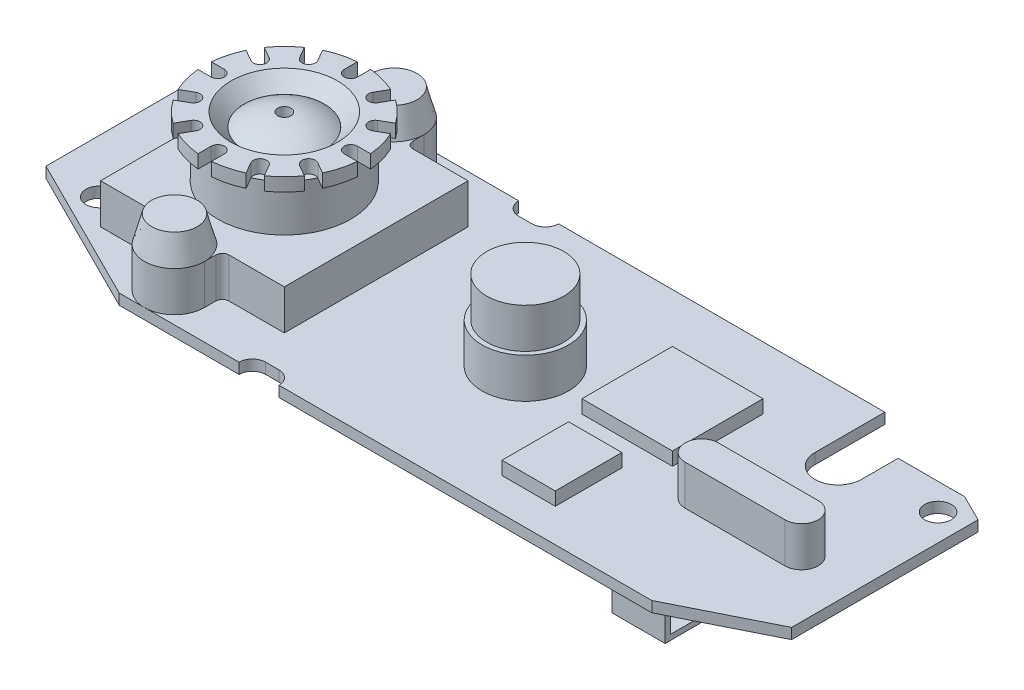
SolidWorks part; units mm, degrees
ref_plane "前基準面" through (0, 0, 0) normal (0, 0, 1) x (1, 0, 0)
ref_plane "上基準面" through (0, 0, 0) normal (0, 1, 0) x (1, 0, 0)
ref_plane "右基準面" through (0, 0, 0) normal (1, 0, 0) x (0, 0, -1)
sketch "草圖1" plane through (0, 0, 0) normal (0, 1, 0) x (1, 0, 0)
  line L0 (0, 0) -> (40355.7531, 0) construction
  line L1 (-20, -10.5) -> (20, -10.5)
  line L2 (20, -10.5) -> (31, -5)
  line L3 (31, -5) -> (31, 5)
  line L4 (31, 5) -> (20, 10.5)
  line L5 (20, 10.5) -> (-20, 10.5)
  line L6 (-20, 10.5) -> (-31, 5)
  line L7 (-31, 5) -> (-31, -5)
  line L8 (-31, -5) -> (-20, -10.5)
  dimension "D1" = 40
  dimension "D2" = 11
  dimension "D3" = 11
  dimension "D4" = 21
  dimension "D5" = 10
  dimension "D6" = 31
  dimension "D7" = 10
extrude "填料-伸長1" add sketch "草圖1" along normal mid plane 0.8
sketch "草圖3" plane through (0, 0.4, 0) normal (0, 1, 0) x (1, 0, 0)
  circle A0 centre (0, 0) radius 3.25
  dimension "D1" = 6.5
extrude "填料-伸長2" add sketch "草圖3" along normal blind 3
sketch "草圖4" plane through (0, 3.4, 0) normal (0, 1, 0) x (1, 0, 0)
  circle A0 centre (0, 0) radius 2.9
  dimension "D1" = 5.8
extrude "填料-伸長3" add sketch "草圖4" along normal blind 3
sketch "草圖5" plane through (0, 0.4, 0) normal (0, 1, 0) x (1, 0, 0)
  line L1 (5.25, 5.8) -> (12.05, 5.8)
  line L2 (5.25, 5.8) -> (5.25, -1)
  line L3 (5.25, -1) -> (12.05, -1)
  line L4 (12.05, 5.8) -> (12.05, -1)
  circle A0 centre (0, 0) radius 3.25 construction
  dimension "D1" = 6.8
  dimension "D2" = 6.8
  dimension "D3" = 1
  dimension "D4" = 2
extrude "填料-伸長4" add sketch "草圖5" along normal blind 1
sketch "草圖6" plane through (0, 0.4, 0) normal (0, 1, 0) x (1, 0, 0)
  line L0 (-10, 10.5) -> (-9, 10.5) construction
  line L1 (20, 10.5) -> (-20, 10.5) construction
  line L2 (-10, 11.5) -> (-9, 11.5)
  line L3 (-10, 9.5) -> (-9, 9.5)
  arc A0 (-10, 11.5) -> (-10, 9.5) centre (-10, 10.5) ccw
  arc A1 (-9, 9.5) -> (-9, 11.5) centre (-9, 10.5) ccw
  point P4 (-9.5, 10.5)
  dimension "D1" = 1
  dimension "D2" = 3
  dimension "D3" = 9
extrude "除料-伸長2" cut sketch "草圖6" against normal blind 1
mirror "鏡射1" about plane through (0, 0, 0) normal (0, 0, 1) of "除料-伸長2"
sketch "草圖9" plane through (0, 0.4, 0) normal (0, 1, 0) x (1, 0, 0)
  line L1 (32.8874, -13.4261) -> (27, -13.4261)
  line L2 (32.8874, -13.4261) -> (32.8874, 12.4209)
  line L3 (32.8874, 12.4209) -> (27, 12.4209)
  line L4 (27, -13.4261) -> (27, 12.4209)
  dimension "D1" = 7
extrude "除料-伸長5" cut sketch "草圖9" against normal blind 1
sketch "草圖7" plane through (0, 0.4, 0) normal (0, 1, 0) x (1, 0, 0)
  line L0 (18.25, 5.25) -> (18.25, 14.2854) construction
  line L1 (16.5, 5.25) -> (16.5, 14.2854)
  line L2 (20, 5.25) -> (20, 14.2854)
  line L3 (20, 10.5) -> (-8, 10.5) construction
  line L5 (12.05, -1) -> (12.05, 5.8) construction
  arc A0 (16.5, 5.25) -> (20, 5.25) centre (18.25, 5.25) ccw
  arc A1 (20, 14.2854) -> (16.5, 14.2854) centre (18.25, 14.2854) ccw
  point P2 (18.25, 9.7677)
  dimension "D1" = 7
  dimension "D2" = 3.5
  dimension "D3" = 6.2
extrude "除料-伸長3" cut sketch "草圖7" against normal blind 1
sketch "草圖8" plane through (0, 0.4, 0) normal (0, 1, 0) x (1, 0, 0)
  line L0 (16.5, 10.5) -> (-8, 10.5) construction
  line L1 (34.7024, 8) -> (19.1327, 8)
  line L2 (34.7024, 8) -> (34.7024, 14.1619)
  line L3 (34.7024, 14.1619) -> (19.1327, 14.1619)
  line L4 (19.1327, 8) -> (19.1327, 14.1619)
  dimension "D1" = 2.5
extrude "除料-伸長4" cut sketch "草圖8" against normal blind 1
sketch "草圖10" plane through (0, 0.4, 0) normal (0, 1, 0) x (1, 0, 0)
  line L0 (-31, 5) -> (-31, -5) construction
  line L1 (-11.2, -6.9) -> (-25, -6.9)
  line L2 (-11.2, -6.9) -> (-11.2, 6.9)
  line L3 (-11.2, 6.9) -> (-25, 6.9)
  line L4 (-25, -6.9) -> (-25, 6.9)
  line L5 (-11.2, -6.9) -> (-25, 6.9) construction
  line L6 (-11.2, 6.9) -> (-25, -6.9) construction
  point P0 (-18.1, 0)
  dimension "D1" = 6
  dimension "D2" = 13.8
  dimension "D3" = 13.8
extrude "填料-伸長5" add sketch "草圖10" along normal blind 3
sketch "草圖11" plane through (0, 3.4, 0) normal (0, 1, 0) x (1, 0, 0)
  line L0 (-18.1, 8.25) -> (-18.1, -8.25) construction
  line L1 (-15.85, 8.25) -> (-15.85, -8.25)
  line L2 (-20.35, 8.25) -> (-20.35, -8.25)
  line L4 (-11.2, -6.9) -> (-11.2, 6.9) construction
  line L5 (-11, 10.5) -> (-20, 10.5) construction
  line L6 (-20, -10.5) -> (-11, -10.5) construction
  arc A0 (-15.85, 8.25) -> (-20.35, 8.25) centre (-18.1, 8.25) ccw
  arc A1 (-20.35, -8.25) -> (-15.85, -8.25) centre (-18.1, -8.25) ccw
  point P2 (-18.1, 0)
  dimension "D1" = 6.9
  dimension "D2" = 4.5
extrude "填料-伸長6" add sketch "草圖11" against normal blind 3
fillet "圓角1" radius 0.5 4 edges at (-15.85, 1.9, -6.9) (-20.35, 1.9, -6.9) (-15.85, 1.9, 6.9) (-20.35, 1.9, 6.9)
sketch "草圖12" plane through (0, 3.4, 0) normal (0, 1, 0) x (1, 0, 0)
  circle A0 centre (-18.1, 8.25) radius 2.25
  circle A1 centre (-18.1, -8.25) radius 2.25
  arc A2 (-15.85, 8.25) -> (-20.35, 8.25) centre (-18.1, 8.25) ccw construction
extrude "填料-伸長7" add sketch "草圖12" along normal blind 2 draft 15
sketch "草圖13" plane through (0, 3.4, 0) normal (0, 1, 0) x (1, 0, 0)
  line L0 (-25, 6.9) -> (-25, -6.9) construction
  line L1 (-20.85, 6.9) -> (-25, 6.9) construction
  circle A0 centre (-18.1, 0) radius 5
  dimension "D3" = 10
  dimension "D1" = 6.9
  dimension "D2" = 6.9
extrude "填料-伸長8" add sketch "草圖13" along normal blind 3.5
sketch "草圖14" plane through (0, 6.9, 0) normal (0, 1, 0) x (1, 0, 0)
  circle A0 centre (-18.1, 0) radius 6
  dimension "D1" = 12
extrude "填料-伸長9" add sketch "草圖14" along normal blind 1
sketch "草圖15" plane through (0, 7.9, 0) normal (0, 1, 0) x (1, 0, 0)
  line L0 (-14.6, 6.0622) -> (-15.6, 4.3301) construction
  line L1 (-14.167, 5.8122) -> (-15.167, 4.0801)
  line L2 (-15.033, 6.3122) -> (-16.033, 4.5801)
  line L3 (-18.1, 0) -> (-18.1, 50000) construction
  line L4 (-15.6, 4.3301) -> (-18.1, 0) construction
  line L5 (-18.1, 0) -> (-7.3659, 0) construction
  line L6 (-18.1, 0) -> (-28.0352, 0) construction
  circle A0 centre (-18.1, 0) radius 6 construction
  arc A1 (-14.167, 5.8122) -> (-15.033, 6.3122) centre (-14.6, 6.0622) ccw
  arc A2 (-16.033, 4.5801) -> (-15.167, 4.0801) centre (-15.6, 4.3301) ccw
  point P4 (-15.1, 5.1962)
  dimension "D1" = 2
  dimension "D2" = 1
  dimension "D3" = 30
extrude "除料-伸長6" cut sketch "草圖15" against normal blind 1
sketch "草圖16" plane through (0, 7.9, 0) normal (0, 1, 0) x (1, 0, 0)
  point P0 (-18.1, 0)
  point P1 (-12.5324, 9.1761)
ref_axis "基準軸1" through (-18.1, 2.3452, 0) along (0, 1, 0)
pattern_circular "環狀複製排列1" count 12 every 30 about axis through (-18.1, 2.3452, 0) along (0, 1, 0) of "除料-伸長6"
sketch "草圖17" plane through (0, 0.4, 0) normal (0, 1, 0) x (1, 0, 0)
  line L0 (5.25, -1) -> (12.05, -1) construction
  line L1 (6.25, -3) -> (10.25, -3)
  line L2 (6.25, -3) -> (6.25, -8)
  line L3 (6.25, -8) -> (10.25, -8)
  line L4 (10.25, -3) -> (10.25, -8)
  line L5 (6.25, -3) -> (10.25, -8) construction
  line L6 (6.25, -8) -> (10.25, -3) construction
  line L7 (5.25, 5.8) -> (5.25, -1) construction
  point P0 (8.25, -5.5)
  dimension "D1" = 5
  dimension "D2" = 4
  dimension "D3" = 2
  dimension "D4" = 1
extrude "填料-伸長10" add sketch "草圖17" along normal up to surface (1 mm away) up to face at (8.65, 1.4, -2.4)
sketch "草圖18" plane through (0, 0.4, 0) normal (0, 1, 0) x (1, 0, 0)
  line L0 (15.25, -2) -> (22.75, -2) construction
  line L1 (15.25, -0.75) -> (22.75, -0.75)
  line L2 (15.25, -3.25) -> (22.75, -3.25)
  line L3 (27, 7) -> (27, -7) construction
  line L4 (-8, -10.5) -> (20, -10.5) construction
  arc A0 (15.25, -0.75) -> (15.25, -3.25) centre (15.25, -2) ccw
  arc A1 (22.75, -3.25) -> (22.75, -0.75) centre (22.75, -2) ccw
  point P2 (19, -2)
  dimension "D1" = 1.25
  dimension "D2" = 10
  dimension "D3" = 3
  dimension "D4" = 8.5
extrude "填料-伸長11" add sketch "草圖18" along normal blind 3
sketch "草圖19" plane through (0, 7.9, 0) normal (0, 1, 0) x (1, 0, 0)
  circle A0 centre (-18.1, 0) radius 3
  dimension "D1" = 6
extrude "除料-伸長7" cut sketch "草圖19" against normal blind 2
chamfer "導角1" distance 1 angle 45 1 edges at (-18.1, 7.9, 3)
sketch "草圖20" plane through (0, 0, 0) normal (0, 0, 1) x (1, 0, 0)
  line L0 (-18.1, 5.9) -> (-18.1, 50005.9) construction
  line L1 (-15.1, 5.9) -> (-21.1, 5.9) construction
  line L2 (-15.1, 6.9) -> (-21.1, 6.9) construction
  line L3 (-15.18, 6.9) -> (-14.0412, 6.9) construction
  line L4 (-14.1, 7.9) -> (-22.1, 7.9) construction
  line L5 (-15.1, 6.9) -> (-18.1, 6.9)
  line L6 (-18.1, 6.9) -> (-18.1, 7.8084)
  line L7 (-18.1, 7.9) -> (-18.1, 7.8084)
  arc A0 (-15.1, 6.9) -> (-18.1, 7.9) centre (-18.1, 2.9) ccw
  point P4 (-18.1, 5.9)
  dimension "D1" = 6
revolve "旋轉1" add sketch "草圖20" angle 360 about L0
sketch "草圖21" plane through (0, 7.9, 0) normal (0, 1, 0) x (1, 0, 0)
  circle A0 centre (-18.1, 0) radius 0.5
  dimension "D1" = 1
extrude "除料-伸長8" cut sketch "草圖21" against normal blind 2
sketch "草圖22" plane through (0, -0.4, 0) normal (0, -1, 0) x (1, 0, 0)
  line L0 (-8, 10.5) -> (20, 10.5) construction
  line L1 (15.5, 3) -> (19.5, 3)
  line L2 (15.5, 3) -> (15.5, 9)
  line L3 (15.5, 9) -> (19.5, 9)
  line L4 (19.5, 3) -> (19.5, 9)
  line L5 (15.5, 3) -> (19.5, 9) construction
  line L6 (15.5, 9) -> (19.5, 3) construction
  line L7 (27, -7) -> (27, 7) construction
  point P0 (17.5, 6)
  dimension "D1" = 1.5
  dimension "D2" = 6
  dimension "D3" = 4
  dimension "D4" = 7.5
extrude "填料-伸長12" add sketch "草圖22" along normal blind 3
sketch "草圖23" plane through (19.5, 0, 0) normal (1, 0, 0) x (0, 0, -1)
  line L0 (-3, -3.4) -> (-9, -3.4) construction
  line L1 (-3.4, -3) -> (-8.6015, -3)
  line L2 (-3.4, -3) -> (-3.4, -0.8)
  line L3 (-3.4, -0.8) -> (-8.6015, -0.8)
  line L4 (-8.6015, -3) -> (-8.6015, -0.8)
  line L5 (-3.4, -3) -> (-8.6015, -0.8) construction
  line L6 (-3.4, -0.8) -> (-8.6015, -3) construction
  line L7 (-3, -0.4) -> (-9, -0.4) construction
  line L8 (-9, -3.4) -> (-9, -0.4) construction
  line L9 (-3, -3.4) -> (-3, -0.4) construction
  point P0 (-6.0007, -1.9)
  dimension "D1" = 0.4
  dimension "D2" = 0.4
  dimension "D3" = 0.3985
  dimension "D4" = 0.4
extrude "除料-伸長9" cut sketch "草圖23" against normal blind 3.5
sketch "草圖24" plane through (0, 0.4, 0) normal (0, 1, 0) x (1, 0, 0)
  line L0 (-31, 5) -> (-31, -5) construction
  line L1 (27, 7) -> (27, -7) construction
  line L2 (20, 8) -> (25, 8) construction
  point P0 (25, 6)
  point P1 (-27, -5)
  dimension "D1" = 4
  dimension "D2" = 2
  dimension "D3" = 5
  dimension "D4" = 2
hole_wizard "Ø2.0mm 定位孔1" positions "3D草圖1" profile "草圖25" hole size "Ø2.0" standard "ISO" end condition through all
sketch3d "3D草圖1"
  point P0 (-27, 0.4, 5)
  point P3 (25, 0.4, -6)
sketch "草圖25" plane through (-27, 0.4, 5) normal (1, 0, 0) x (0, 0, 1)
  line L0 (0, 0) -> (0, 3.8)
  line L1 (0, 3.8) -> (1, 3.8)
  line L2 (1, 3.8) -> (1, 0)
  line L5 (1, 0) -> (0, 0)
  line L11 (0, -6.35) -> (0, 107.95) construction
  dimension "貫穿孔直徑" = 2
  dimension "貫穿孔深度" = 3.8
